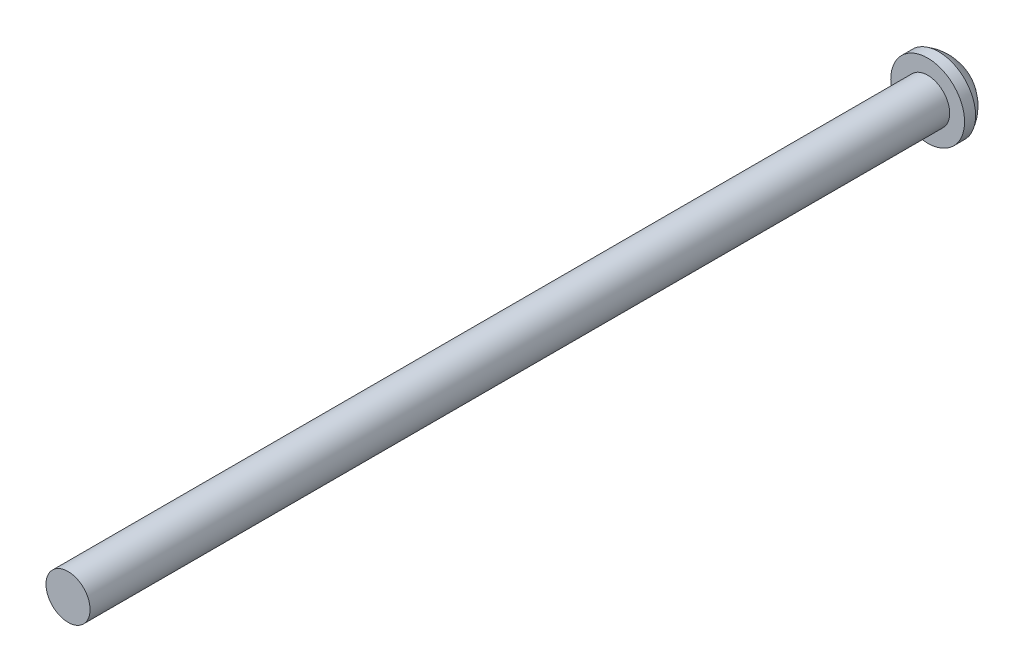
SolidWorks part; units mm, degrees
material "Alloy Steel"
ref_plane "Front" through (0, 0, 0) normal (0, 0, 1) x (1, 0, 0)
ref_plane "Top" through (0, 0, 0) normal (0, 1, 0) x (1, 0, 0)
ref_plane "Right" through (0, 0, 0) normal (1, 0, 0) x (0, 0, -1)
sketch "Sketch1" plane through (0, 0, 0) normal (0, 0, 1) x (1, 0, 0)
  circle A0 centre (0, 0) radius 2
  dimension "D1" = 4
extrude "Extrude1" add sketch "Sketch1" along normal blind 78
sketch "Sketch2" plane through (0, 0, 0) normal (0, 0, -1) x (-1, 0, 0)
  circle A0 centre (0, 0) radius 3.35
  dimension "D1" = 6.7
extrude "Extrude2" add sketch "Sketch2" along normal blind 1
dome "Dome1" faces to dome 1 distance 2 reverse direction no elliptical dome no face at (-3.35, 0, -1) parameters "D1"=2
